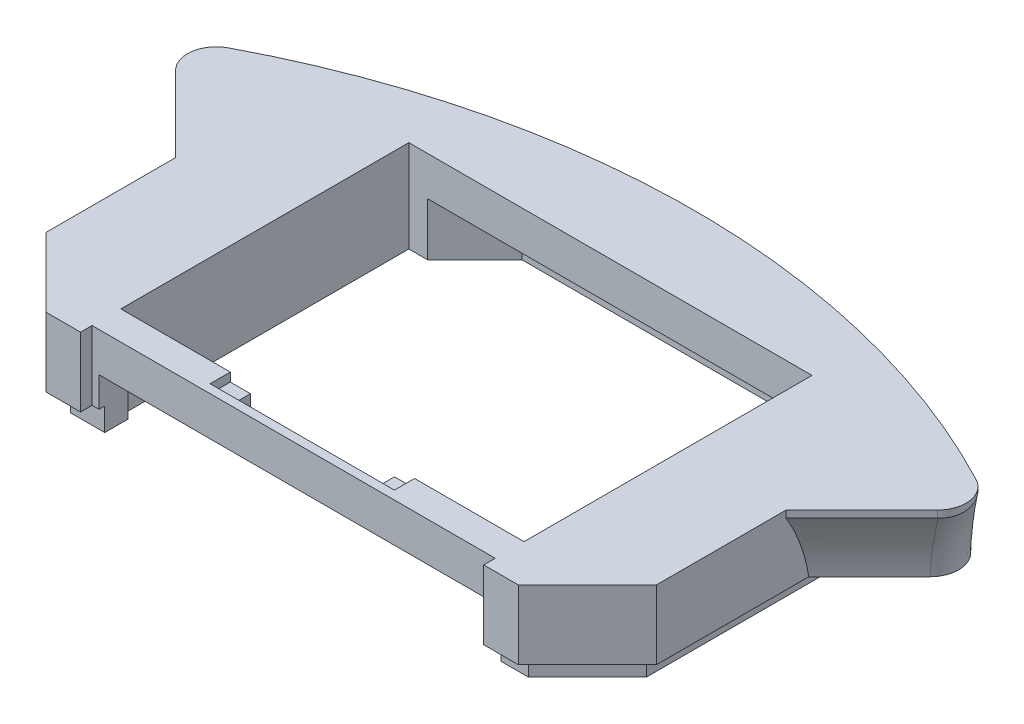
SolidWorks part; units mm, degrees
ref_plane "Front Plane" through (0, 0, 0) normal (0, 0, 1) x (1, 0, 0)
ref_plane "Top Plane" through (0, 0, 0) normal (0, 1, 0) x (1, 0, 0)
ref_plane "Right Plane" through (0, 0, 0) normal (1, 0, 0) x (0, 0, -1)
sketch "Sketch1" plane through (0, 0, 0) normal (0, 1, 0) x (1, 0, 0)
  line L0 (-53, 129.1478) -> (-53, 80)
  line L1 (-53, 80) -> (-41, 68)
  line L2 (-41, 68) -> (41, 68)
  line L3 (41, 68) -> (53, 80)
  line L4 (53, 80) -> (53, 129.1478)
  arc A0 (-53, 129.1478) -> (53, 129.1478) centre (0, 0) cw
  dimension "D1" = 139.6
  dimension "D2" = 68
  dimension "D3" = 80
  dimension "D4" = 135
  dimension "D5" = 53
  dimension "D6" = 106
extrude "Boss-Extrude1" add sketch "Sketch1" along normal blind 16
sketch "Sketch2" plane through (0, 0, 0) normal (0, -1, 0) x (1, 0, 0)
  line L0 (-33.8, -122.9657) -> (-33.8, -62.4)
  line L1 (-23.4, -132.8) -> (24.6, -132.8) construction
  line L2 (-33.4, -122.8) -> (-33.4, -62.8) construction
  line L3 (-33.4, -62.8) -> (34.6, -62.8) construction
  line L4 (34.6, -122.8) -> (34.6, -62.8) construction
  line L5 (-33.8, -62.4) -> (35, -62.4)
  line L6 (35, -122.9657) -> (35, -62.4)
  line L7 (24.7657, -133.2) -> (35, -122.9657)
  line L8 (-23.5657, -133.2) -> (24.7657, -133.2)
  line L9 (-33.8, -122.9657) -> (-23.5657, -133.2)
  line L10 (-33.4, -122.8) -> (-23.4, -132.8) construction
  line L12 (24.6, -132.8) -> (34.6, -122.8) construction
  dimension "D1" = 68
  dimension "D2" = 70
  dimension "D3" = 62.8
  dimension "D4" = 34.6
  dimension "D6" = 10
  dimension "D7" = 135
  dimension "D5" = 0.4
extrude "Cut-Extrude1" cut sketch "Sketch2" against normal offset from surface (9.2 mm away) 6.8 up to face at (0, 16, -94.1246)
sketch "Sketch3" plane through (0, 16, 0) normal (0, 1, 0) x (1, 0, 0)
  line L1 (-35, 125) -> (35, 125)
  line L2 (-35, 125) -> (-35, 75)
  line L3 (-35, 75) -> (35, 75)
  line L4 (35, 125) -> (35, 75)
  dimension "D1" = 75
  dimension "D2" = 70
  dimension "D3" = 50
  dimension "D4" = 35
extrude "Cut-Extrude2" cut sketch "Sketch3" against normal up to next
sketch "Sketch7" plane through (0, 0, 0) normal (0, -1, 0) x (1, 0, 0)
  line L41 (-50, -81.2426) -> (-50, -127.1203)
  line L42 (50, -127.1203) -> (50, -81.2426)
  line L43 (50, -81.2426) -> (39.7574, -71)
  line L44 (39.7574, -71) -> (35, -71)
  line L45 (-33.8, -71) -> (-39.7574, -71)
  line L46 (35, -71) -> (-33.8, -71)
  line L47 (-39.7574, -71) -> (-50, -81.2426)
  line L48 (-50, -81.2426) -> (-50, -127.1203)
  line L49 (50, -127.1203) -> (50, -81.2426)
  line L50 (50, -81.2426) -> (39.7574, -71)
  line L51 (39.7574, -71) -> (35, -71)
  line L52 (-33.8, -71) -> (-39.7574, -71)
  line L53 (35, -71) -> (-33.8, -71)
  line L54 (-39.7574, -71) -> (-50, -81.2426)
  arc A3 (-50, -127.1203) -> (50, -127.1203) centre (0, 0) ccw
  arc A4 (-50, -127.1203) -> (50, -127.1203) centre (0, 0) ccw
  dimension "D1" = 3
extrude "Cut-Extrude5" cut sketch "Sketch7" against normal blind 4 flip side to cut
sketch "Sketch8" plane through (0, 16, 0) normal (0, 1, 0) x (1, 0, 0)
  line L0 (70.8106, 120.308) -> (53, 102.4975)
  line L2 (0, 0) -> (95.9331, 95.9331) construction
  line L3 (53, 129.1478) -> (53, 102.4975)
  line L4 (53, 80) -> (53, 129.1478) construction
  arc A0 (53, 129.1478) -> (70.8106, 120.308) centre (0, 0) cw
  arc A2 (53, 129.1478) -> (-53, 129.1478) centre (0, 0) ccw construction
  dimension "D1" = 45
  dimension "D2" = 35
extrude "Boss-Extrude3" add sketch "Sketch8" against normal up to surface (12 mm away) up to face at (0.15, 4, -88.1846)
ref_plane "Plane1" through (95.5593, 0, -95.5593) normal (-0.7071, 0, 0.7071) x (0, 1, 0)
mirror "Mirror1" about plane through (0, 0, 0) normal (1, 0, 0) of "Boss-Extrude3"
sketch "Sketch9" plane through (95.5593, 0, -95.5593) normal (-0.7071, 0, 0.7071) x (0, 1, 0)
  line L0 (4, 35) -> (16, 35) construction
  line L1 (16, 19.0919) -> (16, 35) construction
  circle A0 centre (0, 0) radius 38
  dimension "D1" = 76
  dimension "D2" = 35
  dimension "D3" = 16
extrude "Cut-Extrude7" cut sketch "Sketch9" along normal up to surface (98.1879 mm away) up to face at (53, 8.5, -91.2487)
ref_plane "Plane2" through (-95.5593, 0, -95.5593) normal (0.7071, 0, 0.7071) x (0, 1, 0)
sketch "Sketch10" plane through (-95.5593, 0, -95.5593) normal (0.7071, 0, 0.7071) x (0, 1, 0)
  line L0 (16, -135.1413) -> (16, -35) construction
  line L1 (4, -35) -> (16, -35) construction
  circle A0 centre (0, 0) radius 38
  dimension "D1" = 76
  dimension "D2" = 16
  dimension "D3" = 35
extrude "Cut-Extrude8" cut sketch "Sketch10" along normal up to surface (22.1879 mm away) up to face at (-53, 8.5, -91.2487)
fillet "Fillet1" radius 5 4 edges at (70.8106, 15.3993, -120.308) (-70.8106, 15.3993, -120.308)
sketch "Sketch12" plane through (0, 16, 0) normal (0, 1, 0) x (1, 0, 0)
  line L0 (-35, 75) -> (35, 75) construction
  line L1 (-12.5, 71.5) -> (12.5, 71.5)
  line L2 (-12.5, 71.5) -> (-12.5, 75)
  line L3 (-12.5, 75) -> (12.5, 75)
  line L4 (12.5, 71.5) -> (12.5, 75)
  dimension "D1" = 71.5
  dimension "D2" = 25
  dimension "D3" = 12.5
extrude "Cut-Extrude10" cut sketch "Sketch12" against normal blind 4
sketch "Sketch13" plane through (0, 16, 0) normal (0, 1, 0) x (1, 0, 0)
  line L0 (12.5, 71.5) -> (12.5, 75) construction
  line L1 (-12.5, 75) -> (-16, 75)
  line L2 (-12.5, 75) -> (-12.5, 71.5)
  line L3 (-12.5, 71.5) -> (-16, 71.5)
  line L4 (-16, 75) -> (-16, 71.5)
  line L5 (12.5, 75) -> (16, 75)
  line L6 (12.5, 75) -> (12.5, 71.5)
  line L7 (12.5, 71.5) -> (16, 71.5)
  line L8 (16, 75) -> (16, 71.5)
extrude "Cut-Extrude11" cut sketch "Sketch13" against normal blind 1.5
sketch "Sketch14" plane through (0, 16, 0) normal (0, 1, 0) x (1, 0, 0)
  line L0 (-41, 68) -> (41, 68) construction
  line L1 (-35, 68) -> (35, 68)
  line L2 (-35, 68) -> (-35, 70)
  line L3 (-35, 70) -> (35, 70)
  line L4 (35, 68) -> (35, 70)
  line L5 (-35, 125) -> (-35, 75) construction
  line L6 (35, 75) -> (35, 125) construction
  dimension "D1" = 2
extrude "Cut-Extrude12" cut sketch "Sketch14" against normal up to next
